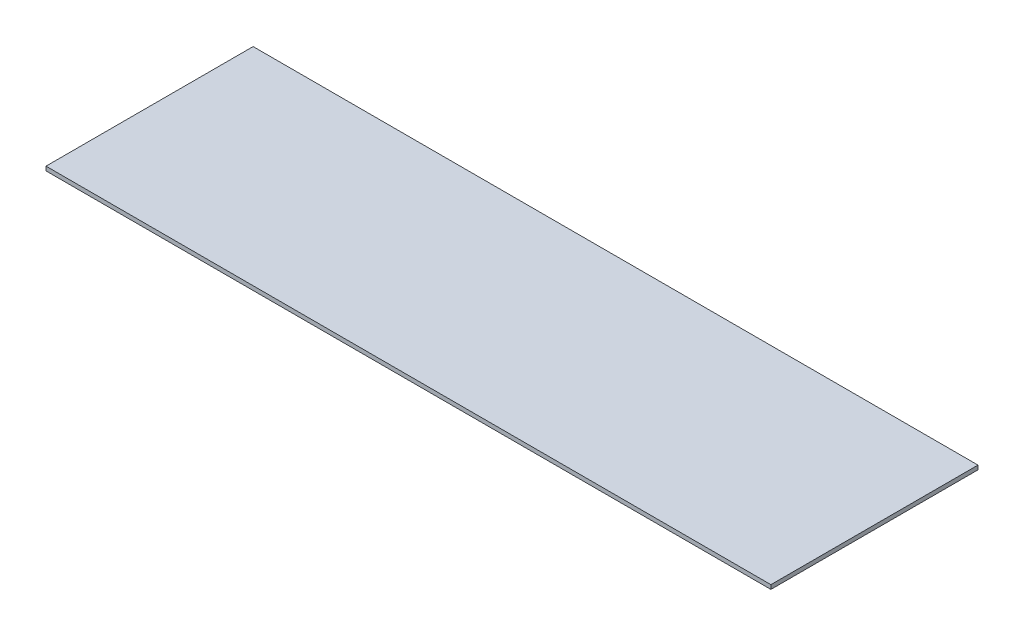
SolidWorks part; units mm, degrees
ref_plane "YX - Front" through (0, 0, 0) normal (0, 0, 1) x (1, 0, 0)
ref_plane "XZ - Top" through (0, 0, 0) normal (0, 1, 0) x (1, 0, 0)
ref_plane "YZ - Right" through (0, 0, 0) normal (1, 0, 0) x (0, 0, -1)
ref_axis "X Axis" through (-80.9, 0, 0) along (1, 0, 0)
ref_axis "Y Axis" through (0, 50, 0) along (0, -1, 0)
ref_axis "Z Axis" through (0, 0, -80.9) along (0, 0, 1)
sketch "Sketch1" plane through (0, 0, 0) normal (0, 1, 0) x (1, 0, 0)
  line L1 (-70, -20) -> (70, -20)
  line L2 (-70, -20) -> (-70, 20)
  line L3 (-70, 20) -> (70, 20)
  line L4 (70, -20) -> (70, 20)
  line L5 (-70, -20) -> (70, 20) construction
  line L6 (-70, 20) -> (70, -20) construction
  point P0 (0, 0)
  dimension "D1" = 40
  dimension "D2" = 140
extrude "Boss-Extrude1" add sketch "Sketch1" along normal blind 0.8
